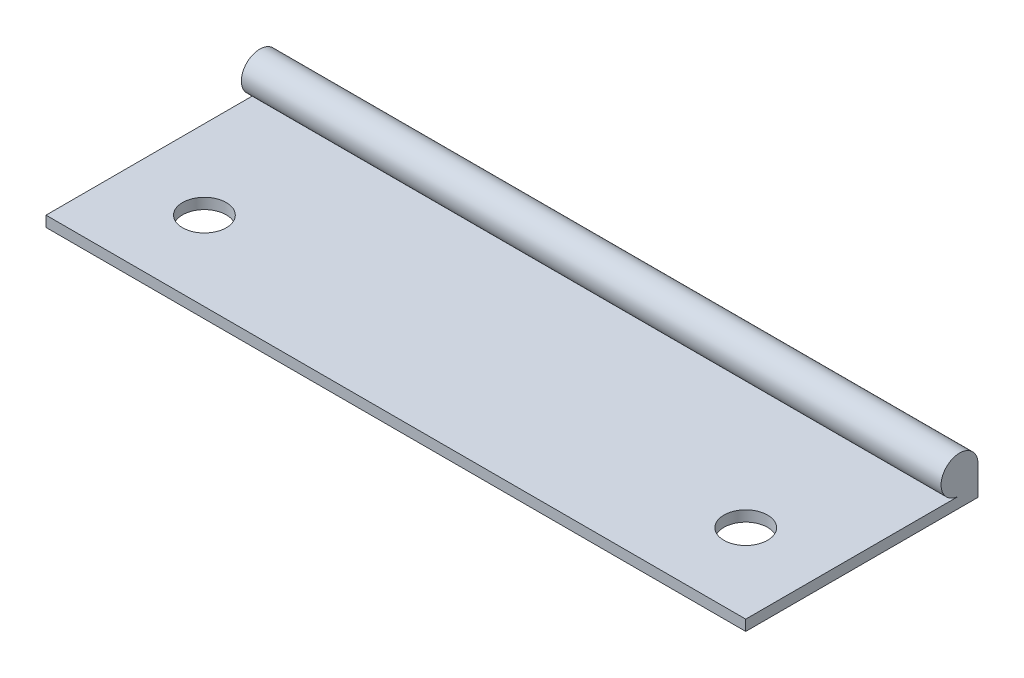
SolidWorks part; units mm, degrees
ref_plane "Front" through (0, 0, 0) normal (0, 0, 1) x (1, 0, 0)
ref_plane "Top" through (0, 0, 0) normal (0, 1, 0) x (1, 0, 0)
ref_plane "Right" through (0, 0, 0) normal (1, 0, 0) x (0, 0, -1)
sketch "草图1" plane through (0, 0, 0) normal (1, 0, 0) x (0, 0, -1)
  line L0 (0, 0) -> (0, 1.1)
  line L1 (0, 1.1) -> (19, 1.1)
  line L2 (0, 0) -> (19, 0)
  line L3 (19, 0) -> (19, 10.8121) construction
  line L4 (19, 1.1) -> (22, 1.1)
  line L5 (19, 0) -> (23.9, 0)
  line L6 (23.9, 0) -> (23.9, 3)
  circle A0 centre (22, 3) radius 3 construction
  circle A1 centre (22, 3) radius 1.9
  dimension "D3" = 6
  dimension "D1" = 1.1
  dimension "D2" = 19
extrude "凸台-拉伸1" add sketch "草图1" along normal blind 72 contours A1 | A1 L4 L1 L0 L2 L5 L6 region at (0, 0.5779, -12.2799) region at (0, 3, -22)
sketch "草图2" plane through (0, 1.1, 0) normal (0, 1, 0) x (1, 0, 0)
  line L0 (0, 8.15) -> (72, 8.15) construction
  line L1 (0, 0) -> (0, 22) construction
  line L2 (72, 0) -> (72, 22) construction
  line L3 (72, 0) -> (0, 0) construction
  circle A0 centre (8.15, 8.15) radius 2.25
  circle A1 centre (63.85, 8.15) radius 2.25
  dimension "D1" = 4.5
  dimension "D2" = 4.5
  dimension "D3" = 8.15
  dimension "D4" = 8.15
  dimension "D5" = 8.15
extrude "切除-拉伸1" cut sketch "草图2" against normal through all
